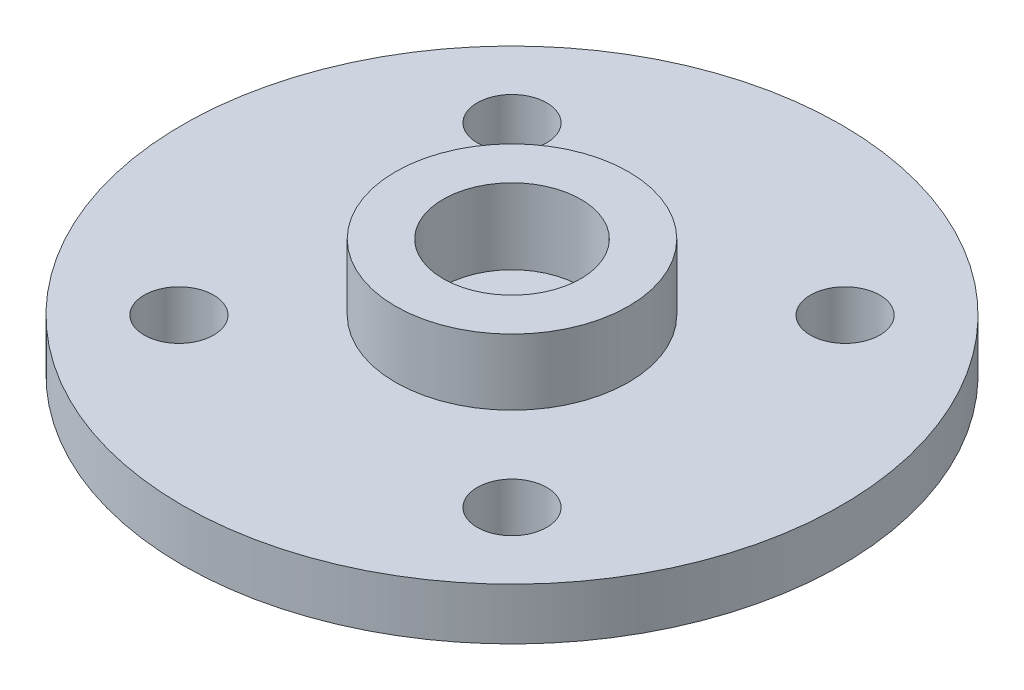
SolidWorks part; units mm, degrees
ref_plane "정면" through (0, 0, 0) normal (0, 0, 1) x (1, 0, 0)
ref_plane "윗면" through (0, 0, 0) normal (0, 1, 0) x (1, 0, 0)
ref_plane "우측면" through (0, 0, 0) normal (1, 0, 0) x (0, 0, -1)
sketch "스케치1" plane through (0, 0, 0) normal (0, 1, 0) x (1, 0, 0)
  line L0 (0, 0) -> (-10.8635, 10.8635) construction
  line L1 (0, 0) -> (-10.1356, 0) construction
  line L2 (-7.075, 7.075) -> (7.075, 7.075) construction
  line L3 (0, 7.075) -> (0, -8.7241) construction
  circle A0 centre (0, 0) radius 14
  circle A1 centre (0, 0) radius 1.5
  circle A2 centre (-7.075, 7.075) radius 1.475
  circle A4 centre (0, 0) radius 4.95
  circle A5 centre (7.075, 7.075) radius 1.475
  circle A6 centre (7.075, -7.075) radius 1.475
  circle A7 centre (-7.075, -7.075) radius 1.475
  dimension "D1" = 28
  dimension "D2" = 3
  dimension "D3" = 9.9
  dimension "D5" = 2.95
  dimension "D4" = 45
  dimension "D6" = 14.15
extrude "보스-돌출1" add sketch "스케치1" along normal blind 2.2 contours A0 A6 A5 A4 A2 A7 region at (-13.604, 0, 0)
extrude "보스-돌출2" add sketch "스케치1<3>" along normal blind 5 contours A4 A1 region at (-4.81, 0, 0)
sketch "스케치1<3>" plane through (0, 0, 0) normal (0, 1, 0) x (1, 0, 0) same geometry as "스케치1"
sketch "스케치2" plane through (0, 5, 0) normal (0, 1, 0) x (1, 0, 0)
  circle A0 centre (0, 0) radius 2.925
  dimension "D1" = 5.85
extrude "컷-돌출1" cut sketch "스케치2" against normal blind 3.2 contours A0
sketch "스케치3" plane through (0, 0, 0) normal (0, -1, 0) x (1, 0, 0)
  line L0 (0, 0) -> (-7.075, 7.075) construction
  line L1 (0.7071, 0.7071) -> (-0.7071, -0.7071)
  line L2 (-0.7071, -0.7071) -> (-2.8284, 1.4142)
  line L3 (0.7071, 0.7071) -> (-1.4142, 2.8284)
  line L4 (-2.8284, 1.4142) -> (-1.4142, 2.8284)
  dimension "D1" = 3
  dimension "D2" = 2
extrude "컷-돌출2" cut sketch "스케치3" against normal blind 1
